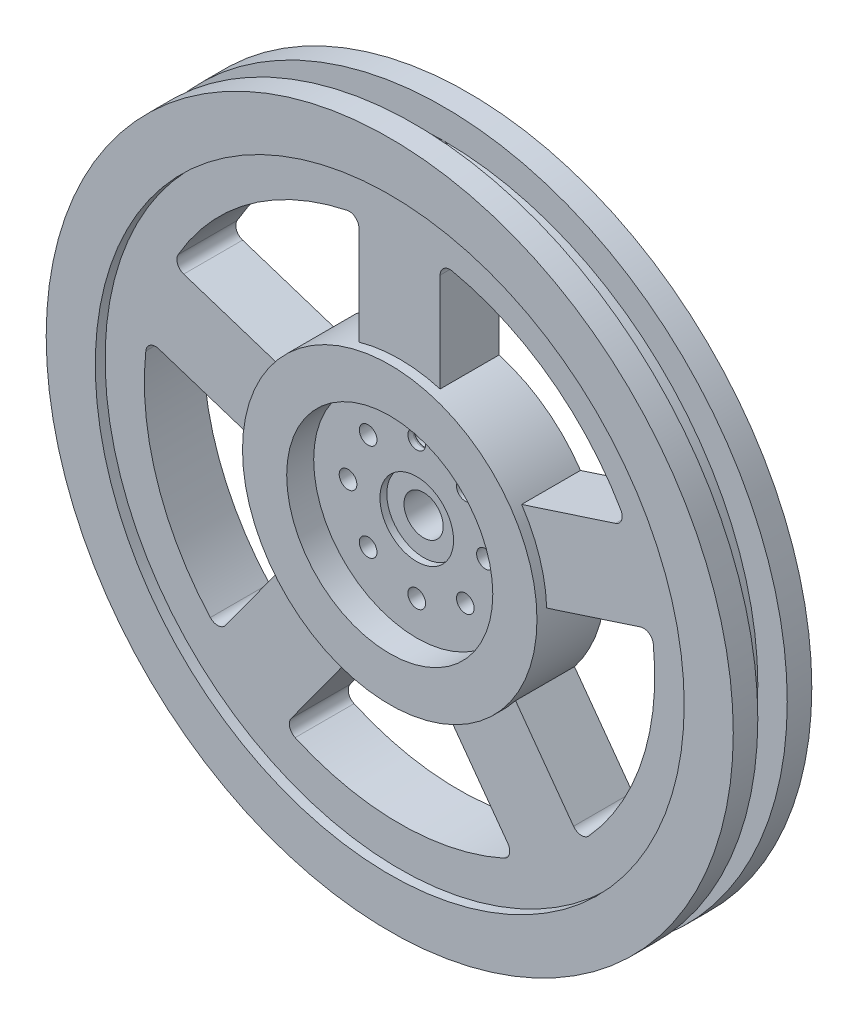
SolidWorks part; units mm, degrees
ref_plane "Front Plane" through (0, 0, 0) normal (0, 0, 1) x (1, 0, 0)
ref_plane "Top Plane" through (0, 0, 0) normal (0, 1, 0) x (1, 0, 0)
ref_plane "Right Plane" through (0, 0, 0) normal (1, 0, 0) x (0, 0, -1)
sketch "Sketch2" plane through (0, 0, 0) normal (0, 1, 0) x (1, 0, 0)
  line L0 (0, -27.7721) -> (0, 23.9685) construction
  line L1 (0, 0) -> (35, 0)
  line L2 (35, 0) -> (35, 2.5)
  line L3 (35, 2.5) -> (32, 2.5)
  line L4 (32, 2.5) -> (32, 5.5)
  line L5 (32, 5.5) -> (35, 5.5)
  line L6 (35, 5.5) -> (35, 8)
  line L7 (35, 8) -> (0, 8)
  line L8 (0, 8) -> (0, 0)
  point P11 (0, 4)
  point P12 (32, 4)
  dimension "D1" = 8
  dimension "D2" = 35
  dimension "D3" = 3
  dimension "D4" = 3
revolve "Revolve1" add sketch "Sketch2" angle 360 about L0
sketch "Sketch3" plane through (0, 0, 0) normal (0, 0, 1) x (1, 0, 0)
  circle A0 centre (0, 0) radius 7.375 construction
  circle A1 centre (0, 7.375) radius 1.25
  circle A2 centre (5.2149, 5.2149) radius 1.25
  circle A3 centre (7.375, 0) radius 1.25
  circle A4 centre (5.2149, -5.2149) radius 1.25
  circle A5 centre (0, -7.375) radius 1.25
  circle A6 centre (-5.2149, -5.2149) radius 1.25
  circle A7 centre (-7.375, 0) radius 1.25
  circle A8 centre (-5.2149, 5.2149) radius 1.25
  point P21 (0, 0)
  dimension "D1" = 8
extrude "Cut-Extrude1" [suppressed] cut sketch "Sketch3" against normal blind 5
sketch "Sketch4" plane through (0, 0, 0) normal (0, 0, 1) x (1, 0, 0)
  circle A0 centre (0, 0) radius 10.5
extrude "Cut-Extrude2" cut sketch "Sketch4" against normal blind 2.75
sketch "Sketch5" plane through (0, 0, -2.75) normal (0, 0, 1) x (1, 0, 0)
  circle A0 centre (0, 0) radius 3.75
extrude "Cut-Extrude3" cut sketch "Sketch5" against normal blind 0.7
sketch "Sketch6" plane through (0, 0, -2.75) normal (0, 0, 1) x (1, 0, 0)
  circle A0 centre (0, 0) radius 7 construction
  circle A1 centre (0, 7) radius 0.9
  circle A2 centre (4.9497, 4.9497) radius 0.9
  circle A3 centre (7, 0) radius 0.9
  circle A4 centre (4.9497, -4.9497) radius 0.9
  circle A5 centre (0, -7) radius 0.9
  circle A6 centre (-4.9497, -4.9497) radius 0.9
  circle A7 centre (-7, 0) radius 0.9
  circle A8 centre (-4.9497, 4.9497) radius 0.9
  point P22 (0, 0)
  dimension "D1" = 8
extrude "Cut-Extrude4" cut sketch "Sketch6" against normal through all
ref_axis "Axis1" through (-7, 0, -8) along (0, 0, 1)
ref_axis "Axis2" through (7, 0, -8) along (0, 0, 1)
ref_plane "Plane2" through (0, 0, 0) normal (0, -1, 0) x (-1, 0, 0)
ref_plane "Plane3" through (0, 35, 0) normal (0, 1, 0) x (1, 0, 0)
sketch "Sketch11" plane through (0, 0, -3.45) normal (0, 0, 1) x (1, 0, 0)
  circle A0 centre (0, 0) radius 2
extrude "Cut-Extrude8" cut sketch "Sketch11" against normal through all
ref_axis "Axis3" through (0, 0, -8) along (0, 0, 1)
ref_plane "Plane4" through (0, 0, 0) normal (-1, 0, 0) x (0, 0, 1)
ref_plane "Plane5" through (0, 32, 0) normal (0, 1, 0) x (1, 0, 0)
sketch "Sketch14" plane through (0, 32, 0) normal (0, 1, 0) x (1, 0, 0)
  line L0 (-7.0769, 4.5) -> (7.6722, 4.5) construction
  line L1 (-32, 5.5) -> (32, 5.5) construction
  circle A0 centre (0, 4.5) radius 1
  dimension "D1" = 1
extrude "Cut-Extrude9" cut sketch "Sketch14" against normal blind 25
ref_axis "Axis5" through (0, 7, -4.5) along (0, 1, 0)
ref_plane "Plane6" through (0, 0, -4.5) normal (0, 0, 1) x (0, 1, 0)
sketch "Sketch17" plane through (0, 0, -4.5) normal (0, 0, 1) x (0, 1, 0)
  circle A0 centre (7, 0) radius 1
  circle A1 centre (7, 0) radius 0.9 construction
extrude "Cut-Extrude11" cut sketch "Sketch17" against normal blind 1 and the other way blind 1 contours A0
fillet "Fillet4" radius 0.3 2 edges at (0.9, 7, -3.5) (0.9, 7, -5.5)
sketch "Sketch18" plane through (0, 0, -8) normal (0, 0, -1) x (-1, 0, 0)
  circle A1 centre (0, 0) radius 30
extrude "Cut-Extrude12" cut sketch "Sketch18" against normal blind 1
sketch "Sketch19" plane through (0, 0, 0) normal (0, 0, 1) x (1, 0, 0)
  circle A0 centre (0, 0) radius 15
  circle A1 centre (0, 0) radius 30
  dimension "D1" = 15
extrude "Cut-Extrude13" cut sketch "Sketch19" against normal blind 1
sketch "Sketch20" plane through (0, 0, -1) normal (0, 0, 1) x (1, 0, 0)
  line L0 (0, 0) -> (15.8158, 21.7686) construction
  line L1 (0, 7) -> (0, 32) construction
  line L2 (12.4356, 8.3879) -> (21.9919, 11.4929)
  line L3 (4.1346, 14.4189) -> (4.1346, 24.467)
  line L4 (0, 0) -> (0, 47.1446) construction
  line L5 (0, 0) -> (4.1346, 14.4189) construction
  circle A0 centre (0, 0) radius 15 construction
  arc A1 (4.1346, 14.4189) -> (12.4356, 8.3879) centre (0, 0) cw
  arc A2 (5.3399, 25.4457) -> (4.1346, 24.467) centre (5.1346, 24.467) ccw
  arc A3 (22.5502, 12.9417) -> (21.9919, 11.4929) centre (21.6829, 12.444) cw
  circle A4 centre (0, 0) radius 15 construction
  arc A5 (5.3399, 25.4457) -> (22.5502, 12.9417) centre (0, 0) cw
  circle A6 centre (0, 0) radius 30 construction
  point P34 (0, 0)
  point P39 (0, 0)
  point P58 (0, 0)
  dimension "D1" = 40
  dimension "D2" = 1
  dimension "D4" = 26
  dimension "D3" = 16
extrude "Cut-Extrude14" cut sketch "Sketch20" against normal through all both and the other way through all
pattern_circular "CirPattern4" count 5 over 360 about axis through (0, 0, 27.7721) along (0, 0, 1) of "Cut-Extrude14"
